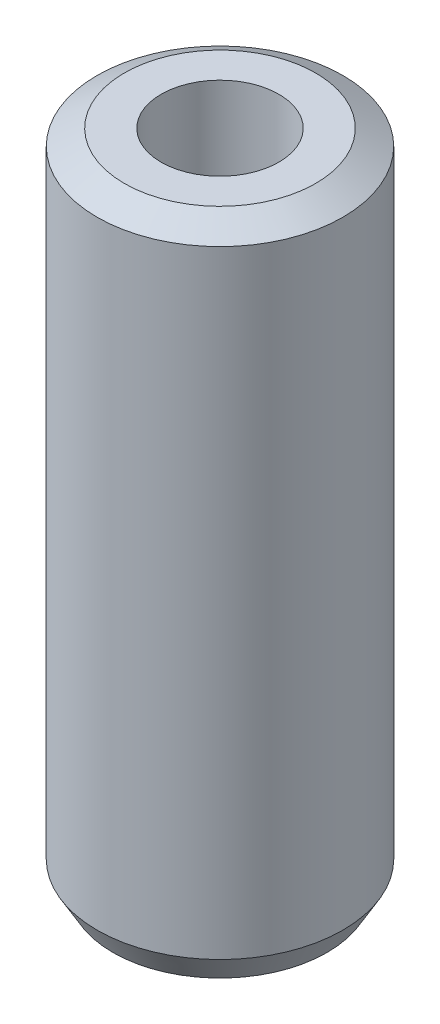
SolidWorks part; units mm, degrees
ref_plane "Front Plane" through (0, 0, 0) normal (0, 0, 1) x (1, 0, 0)
ref_plane "Top Plane" through (0, 0, 0) normal (0, 1, 0) x (1, 0, 0)
ref_plane "Right Plane" through (0, 0, 0) normal (1, 0, 0) x (0, 0, -1)
sketch "Sketch1" plane through (0, 0, 0) normal (0, 1, 0) x (1, 0, 0)
  circle A0 centre (0, 0) radius 40
  dimension "SHAFT_OD" = 80
extrude "Boss-Extrude1" add sketch "Sketch1" along normal blind 214.9605
sketch "Sketch2" plane through (0, 0, 0) normal (0, 1, 0) x (1, 0, 0)
  circle A0 centre (0, 0) radius 19.167
  dimension "BORE_D" = 38.3341
extrude "Cut-Extrude1" cut sketch "Sketch2" along normal through all
chamfer "Chamfer1" distance 5.1056 angle 60 2 edges at (0, 214.9605, 40) (0, 0, 40) first distance on face at (0, 214.9605, 40) first distance on face at (0, 0, 19.167)
